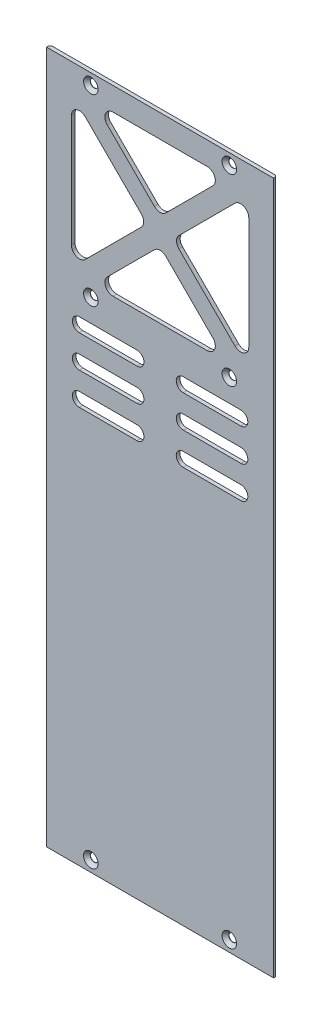
SolidWorks part; units mm, degrees
material "6061-T6 (SS)"
ref_plane "Front Plane" through (0, 0, 0) normal (0, 0, 1) x (1, 0, 0)
ref_plane "Top Plane" through (0, 0, 0) normal (0, 1, 0) x (1, 0, 0)
ref_plane "Right Plane" through (0, 0, 0) normal (1, 0, 0) x (0, 0, -1)
sketch "Sketch1" plane through (0, 0, 0) normal (0, 0, 1) x (1, 0, 0)
  line L1 (49.2063, -150) -> (-49.2062, -150)
  line L2 (49.2063, -150) -> (49.2063, 150)
  line L3 (49.2063, 150) -> (-49.2062, 150)
  line L4 (-49.2062, -150) -> (-49.2062, 150)
  line L5 (49.2063, -150) -> (-49.2062, 150) construction
  line L6 (49.2063, 150) -> (-49.2062, -150) construction
  point P0 (0, 0)
  dimension "D1" = 300
  dimension "D2" = 98.4125
extrude "Boss-Extrude1" add sketch "Sketch1" along normal mid plane 1.5875
chamfer "Chamfer1" distance 0.7937 angle 45 2 edges at (-49.2062, 0, -0.7937) (49.2063, 0, -0.7937)
sketch "Sketch2" plane through (0, 0, -0.7937) normal (0, 0, -1) x (-1, 0, 0)
  line L1 (0, 111.1319) -> (28.8681, 140)
  line L2 (28.8681, 140) -> (-28.8681, 140)
  line L4 (-38.4125, 138.2306) -> (-5.6569, 105.475)
  line L5 (-5.6569, 105.475) -> (-38.4125, 72.7194)
  line L6 (-38.4125, 72.7194) -> (-38.4125, 138.2306)
  line L7 (-28.8681, 70.95) -> (28.8681, 70.95)
  line L8 (28.8681, 70.95) -> (0, 99.8181)
  line L9 (0, 99.8181) -> (-28.8681, 70.95)
  line L10 (38.4125, 72.7194) -> (5.6569, 105.475)
  line L11 (5.6569, 105.475) -> (38.4125, 138.2306)
  line L12 (38.4125, 138.2306) -> (38.4125, 72.7194)
  line L13 (-48.4125, 150) -> (48.4125, 150) construction
  line L14 (-48.4125, 150) -> (-48.4125, -150) construction
  line L15 (48.4125, -150) -> (48.4125, 150) construction
  line L16 (-28.8681, 140) -> (0, 111.1319)
  line L17 (0, 99.8181) -> (0, 111.1319)
  line L18 (-5.6569, 105.475) -> (5.6569, 105.475)
  line L19 (-35, 52.95) -> (-10, 52.95) construction
  line L20 (-35, 55.95) -> (-10, 55.95)
  line L21 (-35, 49.95) -> (-10, 49.95)
  line L22 (-35, 38.95) -> (-10, 38.95) construction
  line L23 (-35, 41.95) -> (-10, 41.95)
  line L24 (-35, 35.95) -> (-10, 35.95)
  line L25 (-35, 24.95) -> (-10, 24.95) construction
  line L26 (-35, 27.95) -> (-10, 27.95)
  line L27 (-35, 21.95) -> (-10, 21.95)
  line L28 (10, 52.95) -> (35, 52.95) construction
  line L29 (10, 55.95) -> (35, 55.95)
  line L30 (10, 49.95) -> (35, 49.95)
  line L31 (10, 38.95) -> (35, 38.95) construction
  line L32 (10, 41.95) -> (35, 41.95)
  line L33 (10, 35.95) -> (35, 35.95)
  line L34 (10, 24.95) -> (35, 24.95) construction
  line L35 (10, 27.95) -> (35, 27.95)
  line L36 (10, 21.95) -> (35, 21.95)
  arc A0 (-35, 55.95) -> (-35, 49.95) centre (-35, 52.95) ccw
  arc A1 (-10, 49.95) -> (-10, 55.95) centre (-10, 52.95) ccw
  arc A2 (-35, 41.95) -> (-35, 35.95) centre (-35, 38.95) ccw
  arc A3 (-10, 35.95) -> (-10, 41.95) centre (-10, 38.95) ccw
  arc A4 (-35, 27.95) -> (-35, 21.95) centre (-35, 24.95) ccw
  arc A5 (-10, 21.95) -> (-10, 27.95) centre (-10, 24.95) ccw
  arc A6 (10, 55.95) -> (10, 49.95) centre (10, 52.95) ccw
  arc A7 (35, 49.95) -> (35, 55.95) centre (35, 52.95) ccw
  arc A8 (10, 41.95) -> (10, 35.95) centre (10, 38.95) ccw
  arc A9 (35, 35.95) -> (35, 41.95) centre (35, 38.95) ccw
  arc A10 (10, 27.95) -> (10, 21.95) centre (10, 24.95) ccw
  arc A11 (35, 21.95) -> (35, 27.95) centre (35, 24.95) ccw
  point P12 (-22.5, 52.95)
  point P25 (-22.5, 38.95)
  point P32 (-22.5, 24.95)
  point P39 (22.5, 52.95)
  point P46 (22.5, 38.95)
  point P53 (22.5, 24.95)
  dimension "D9" = 3
  dimension "D1" = 10
  dimension "D2" = 10
  dimension "D3" = 10
  dimension "D4" = 79.05
  dimension "D5" = 8
  dimension "D6" = 8
  dimension "D7" = 8
  dimension "D8" = 25
  dimension "D10" = 20
  dimension "D11" = 10
  dimension "D12" = 8
  dimension "D13" = 8
  dimension "D14" = 15
extrude "Cut-Extrude1" cut sketch "Sketch2" against normal through all contours L8 L9 L7 | L6 L5 L4 | L2 L16 L1 | L12 L11 L10 | L30 A7 L29 A6 | L27 A5 L26 A4 | L20 A1 L21 A0 | L23 A3 L24 A2 | L32 A9 L33 A8 | L35 A11 L36 A10 region at (0, 130.3773, -0.7937) region at (-27.494, 105.475, -0.7937) region at (0, 80.5727, -0.7937) region at (27.494, 105.475, -0.7937) region at (22.5, 24.95, -0.7937) region at (-22.5, 52.95, -0.7937)
fillet "Fillet1" radius 3.5 12 edges at (-5.6569, 105.475, 0) (-38.4125, 138.2306, 0) (-28.8681, 140, 0) (0, 111.1319, 0) (28.8681, 140, 0) (38.4125, 138.2306, 0) (5.6569, 105.475, 0) (-28.8681, 70.95, 0) (0, 99.8181, 0) (-38.4125, 72.7194, 0) (28.8681, 70.95, 0) (38.4125, 72.7194, 0)
sketch "Sketch5" plane through (0, 0, 0.7937) normal (0, 0, 1) x (1, 0, 0)
  line L0 (-49.2062, -150) -> (49.2063, -150) construction
  line L1 (49.2063, 150) -> (-49.2062, 150) construction
  point P0 (-30, -145.225)
  point P2 (30, -145.225)
  point P4 (-30, 65.7)
  point P6 (30, 65.7)
  point P8 (30, 145.225)
  point P10 (-30, 145.225)
  dimension "D1" = 30
  dimension "D2" = 30
  dimension "D3" = 4.775
  dimension "D4" = 4.775
  dimension "D5" = 79.525
hole_wizard "CSK for M3 Flat Head Machine Screw1" positions "Sketch5" profile "Sketch4" countersink size "M3" standard "ANSI Metric"
sketch "Sketch4" plane through (-30, -145.225, 0.7937) normal (1, 0, 0) x (0, -1, 0)
  line L0 (0, 0) -> (0, 8.6175)
  line L1 (0, 8.6175) -> (1.7, 7.596)
  line L2 (1.7, 7.596) -> (1.7, 1.45)
  line L3 (1.7, 1.45) -> (3.15, 0)
  line L5 (3.15, 0) -> (0, 0)
  line L6 (-1.7, 1.45) -> (-3.15, 0) construction
  line L10 (0, 8.6175) -> (-1.7, 7.596) construction
  line L11 (0, -6.35) -> (0, 107.95) construction
  dimension "Hole Dia." = 3.4
  dimension "Hole Depth" = 7.596
  dimension "Near C'Sink Dia." = 6.3
  dimension "Near C'Sink Angle" = 90
  dimension "Drill Angle" = 118
